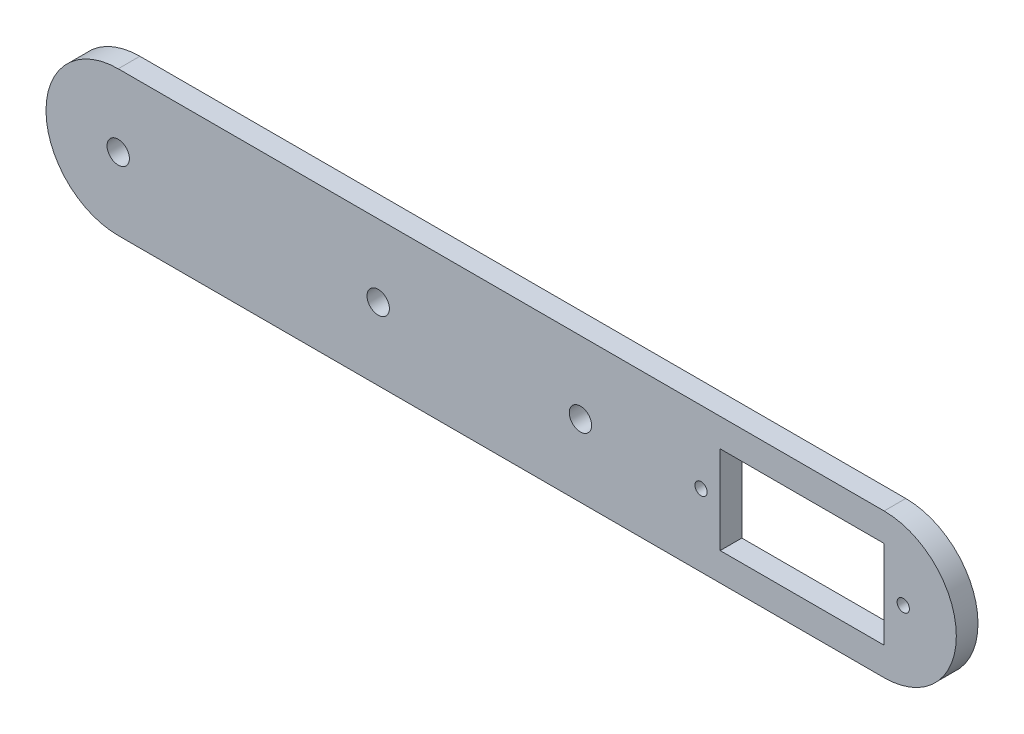
SolidWorks part; units mm, degrees
ref_plane "Front Plane" through (0, 0, 0) normal (0, 0, 1) x (1, 0, 0)
ref_plane "Top Plane" through (0, 0, 0) normal (0, 1, 0) x (1, 0, 0)
ref_plane "Right Plane" through (0, 0, 0) normal (1, 0, 0) x (0, 0, -1)
sketch "Sketch1" plane through (0, 0, 0) normal (0, 0, 1) x (1, 0, 0)
  line L0 (-58.0586, 14.1911) -> (47.9914, 14.1911) construction
  line L1 (-58.0586, 24.1911) -> (47.9914, 24.1911)
  line L2 (-58.0586, 4.1911) -> (47.9914, 4.1911)
  arc A0 (-58.0586, 24.1911) -> (-58.0586, 4.1911) centre (-58.0586, 14.1911) ccw
  arc A1 (47.9914, 4.1911) -> (47.9914, 24.1911) centre (47.9914, 14.1911) ccw
  point P2 (-5.0336, 14.1911)
extrude "Boss-Extrude1" add sketch "Sketch1" along normal blind 3
sketch "Sketch3" plane through (0, 0, 3) normal (0, 0, 1) x (1, 0, 0)
  circle A0 centre (-58.0586, 14.1911) radius 1.55
  arc A1 (-58.0586, 24.1911) -> (-58.0586, 4.1911) centre (-58.0586, 14.1911) ccw construction
extrude "Cut-Extrude2" cut sketch "Sketch3" against normal blind 3 contours A0
sketch "Sketch4" plane through (9.9795, 1.4333, 3) normal (0, 0, 1) x (1, 0, 0)
  line L0 (-68.0381, 2.7578) -> (38.0119, 2.7578) construction
  circle A0 centre (-4.0381, 12.7578) radius 1.55
  arc A2 (38.0119, 2.7578) -> (38.0119, 22.7578) centre (38.0119, 12.7578) ccw construction
  dimension "D1" = 10
  dimension "D2" = 42.05
extrude "Cut-Extrude4" cut sketch "Sketch4" against normal blind 3
sketch "Sketch5" plane through (-9.9795, 1.4333, 0) normal (0, 0, -1) x (-1, 0, 0)
  line L0 (-57.9708, 22.7578) -> (48.0792, 22.7578) construction
  circle A0 centre (12.0792, 12.7578) radius 1.55
  arc A2 (48.0792, 2.7578) -> (48.0792, 22.7578) centre (48.0792, 12.7578) ccw construction
  dimension "D1" = 10
  dimension "D2" = 36
extrude "Cut-Extrude6" cut sketch "Sketch5" against normal blind 3
sketch "Sketch6" plane through (0, 0, 3) normal (0, 0, 1) x (1, 0, 0)
  line L0 (47.9914, 24.1911) -> (-58.0586, 24.1911) construction
  line L1 (25.2914, 20.2911) -> (47.9914, 20.2911)
  line L2 (25.2914, 20.2911) -> (25.2914, 8.0911)
  line L3 (25.2914, 8.0911) -> (47.9914, 8.0911)
  line L4 (47.9914, 20.2911) -> (47.9914, 8.0911)
  arc A2 (47.9914, 4.1911) -> (47.9914, 24.1911) centre (47.9914, 14.1911) ccw construction
  point P7 (47.9914, 14.1911)
  point P10 (57.9914, 14.1911)
  dimension "D1" = 10
  dimension "D2" = 10
  dimension "D3" = 22.7
  dimension "D4" = 12.2
extrude "Cut-Extrude7" cut sketch "Sketch6" against normal blind 3
sketch "Sketch7" plane through (0, 0, 0) normal (0, 0, -1) x (-1, 0, 0)
  line L0 (-25.2914, 20.2911) -> (-25.2914, 8.0911) construction
  line L1 (-47.9914, 24.1911) -> (58.0586, 24.1911) construction
  line L2 (-47.9914, 8.0911) -> (-47.9914, 20.2911) construction
  circle A0 centre (-22.6414, 14.1911) radius 0.85
  circle A1 centre (-50.6414, 14.1911) radius 0.85
  dimension "D1" = 1.7
  dimension "D2" = 2.65
  dimension "D5" = 2.65
  dimension "D6" = 1.7
  dimension "D3" = 10
  dimension "D4" = 10
extrude "Cut-Extrude8" cut sketch "Sketch7" against normal blind 3
